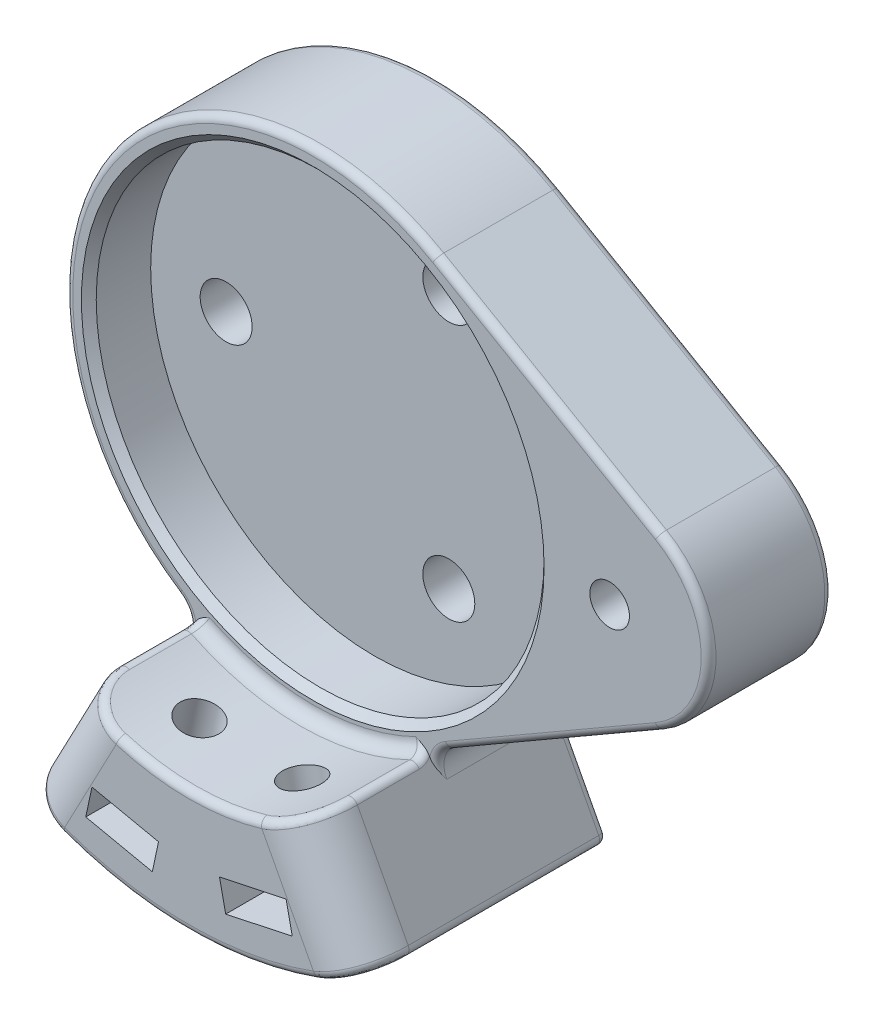
SolidWorks part; units mm, degrees
ref_plane "Plan de face" through (0, 0, 0) normal (0, 0, 1) x (1, 0, 0)
ref_plane "Plan de dessus" through (0, 0, 0) normal (0, 1, 0) x (1, 0, 0)
ref_plane "Plan de droite" through (0, 0, 0) normal (1, 0, 0) x (0, 0, -1)
ref_axis "Axe1" through (0, 0, -0.5) along (0, 0, 1)
ref_plane "Plan2" through (0, 0, 0) normal (-0.2079, 0.9781, 0) x (0, 0, 1)
sketch "Esquisse1" plane through (0, 0, 0) normal (0, 0, 1) x (1, 0, 0)
  line L0 (10, 17.3205) -> (28, 6.9282)
  line L1 (28, -6.9282) -> (10, -17.3205)
  arc A0 (10, 17.3205) -> (10, -17.3205) centre (0, 0) ccw
  arc A1 (28, -6.9282) -> (28, 6.9282) centre (24, 0) ccw
  dimension "D2" = 20
  dimension "D3" = 8
  dimension "D1" = 24
extrude "Boss.-Extru.1" add sketch "Esquisse1" along normal blind 10
sketch "Esquisse2" plane through (0, 0, 10) normal (0, 0, 1) x (1, 0, 0)
  circle A0 centre (0, 0) radius 18.1
  dimension "D1" = 36.2
extrude "Enlèv. mat.-Extru.1" cut sketch "Esquisse2" against normal blind 5
sketch "Esquisse3" plane through (0, 0, 5) normal (0, 0, 1) x (1, 0, 0)
  line L0 (-12, 0) -> (0, 0) construction
  circle A0 centre (-12, 0) radius 2.1
  dimension "D1" = 4.2
  dimension "D2" = 12
extrude "Enlèv. mat.-Extru.2" cut sketch "Esquisse3" against normal through all
pattern_circular "Répétition circulaire1" count 3 over 360 about axis through (0, 0, 5) along (0, 0, 1) of "Enlèv. mat.-Extru.2" reverse direction yes
sketch "Esquisse4" plane through (0, 0, 10) normal (0, 0, 1) x (1, 0, 0)
  circle A0 centre (24, 0) radius 1.6
  dimension "D1" = 3.2
extrude "Enlèv. mat.-Extru.3" cut sketch "Esquisse4" against normal through all
sketch "Esquisse5" plane through (0, 0, 0) normal (0, 0, -1) x (-1, 0, 0)
  circle A0 centre (-24, 0) radius 4
  dimension "D1" = 8
extrude "Enlèv. mat.-Extru.4" cut sketch "Esquisse5" against normal offset from surface (7 mm away) 3 up to face at (25.6, 0, 10)
ref_plane "Plan1" through (0, 0, 5) normal (0, 0, -1) x (-1, 0, 0)
sketch "Esquisse7" plane through (0, 0, 0) normal (0, 0, -1) x (-1, 0, 0)
  line L0 (9.3333, -17.6887) -> (14, -26.533)
  line L1 (-9.3333, -17.6887) -> (-14, -26.533)
  line L3 (0, 0) -> (0, -30) construction
  arc A0 (-14, -26.533) -> (14, -26.533) centre (0, 0) ccw
  arc A1 (-10, -17.3205) -> (-10, 17.3205) centre (0, 0) ccw construction
  arc A2 (-9.3333, -17.6887) -> (9.3333, -17.6887) centre (0, 0) ccw
  dimension "D1" = 60
  dimension "D2" = 28
extrude "Boss.-Extru.2" add sketch "Esquisse7" against normal blind 20
fillet "Congé5" radius 4 2 edges at (11.6667, -22.1108, 20) (-11.6667, -22.1108, 20) tangent propagation no
fillet "Congé2" radius 2 2 edges at (-9.3333, -17.6887, 5) (9.3333, -17.6887, 5)
fillet "Congé4" radius 1 1 edges at (0, -20, 10)
sketch "Esquisse8" plane through (0, 0, 0) normal (-0.2079, 0.9781, 0) x (0, 0, 1)
  line L1 (-0.5, 0) -> (10.5, 0) construction
  line L2 (5, 26.84) -> (5, -26.84) construction
  circle A0 centre (15, 0) radius 1.6
  dimension "D1" = 3.2
  dimension "D2" = 10
extrude "Enlèv. mat.-Extru.5" cut sketch "Esquisse8" against normal through all
sketch "Esquisse9" plane through (0, 0, 0) normal (-0.2079, 0.9781, 0) x (0, 0, 1)
  line L0 (16.5877, 2.75) -> (20, 2.75)
  line L1 (13.4123, -2.75) -> (16.5877, -2.75)
  line L2 (16.5877, -2.75) -> (18.1754, 0) construction
  line L3 (18.1754, 0) -> (16.5877, 2.75) construction
  line L4 (16.5877, 2.75) -> (13.4123, 2.75)
  line L5 (13.4123, 2.75) -> (11.8246, 0)
  line L6 (11.8246, 0) -> (13.4123, -2.75)
  line L8 (20, 2.75) -> (20, -2.75)
  line L9 (20, -2.75) -> (16.5877, -2.75)
  line L10 (20, -15.9667) -> (20, 4.256) construction
  circle A0 centre (15, 0) radius 2.75 construction
  dimension "D1" = 5.5
extrude "Enlèv. mat.-Extru.6" cut sketch "Esquisse9" along normal mid plane 2.4 from offset 26 offset against normal yes
mirror "Symétrie1" about plane through (0, 0, 0) normal (1, 0, 0) of "Enlèv. mat.-Extru.6", "Enlèv. mat.-Extru.5"
fillet "Congé1" radius 0.6 27 edges at (-17.0497, 10.455, 10) (19, 12.1244, 10) (32, 0, 10) (-17.0497, 10.455, 0) (19, 12.1244, 0) (32, 0, 0) (19.5037, -11.8335, 10) (19.5037, -11.8335, 0) (-10.0574, -17.9404, 10) (12.1193, -22.9686, 0) (-12.1121, -22.955, 0) (-10.0574, -17.9404, 0) (0, -30, 0) (0, -20, 20) (0, -30, 20) (10.0858, -17.9166, 10) (10.0858, -17.9166, 0) (14, -26.533, 8) (13.2191, -26.9306, 18.4984) (-14, -26.533, 8) (-12.6459, -27.2044, 19.1312) (-9.1966, -17.4296, 10.2929) (-9.3333, -17.6887, 13.5) (-8.5497, -18.0804, 18.498) (9.1966, -17.4296, 10.2929) (9.3333, -17.6887, 13.5) (7.959, -18.3481, 19.141)
chamfer "Chanfrein1" distance 0.6 angle 45 1 edges at (18.1, 0, 10)
